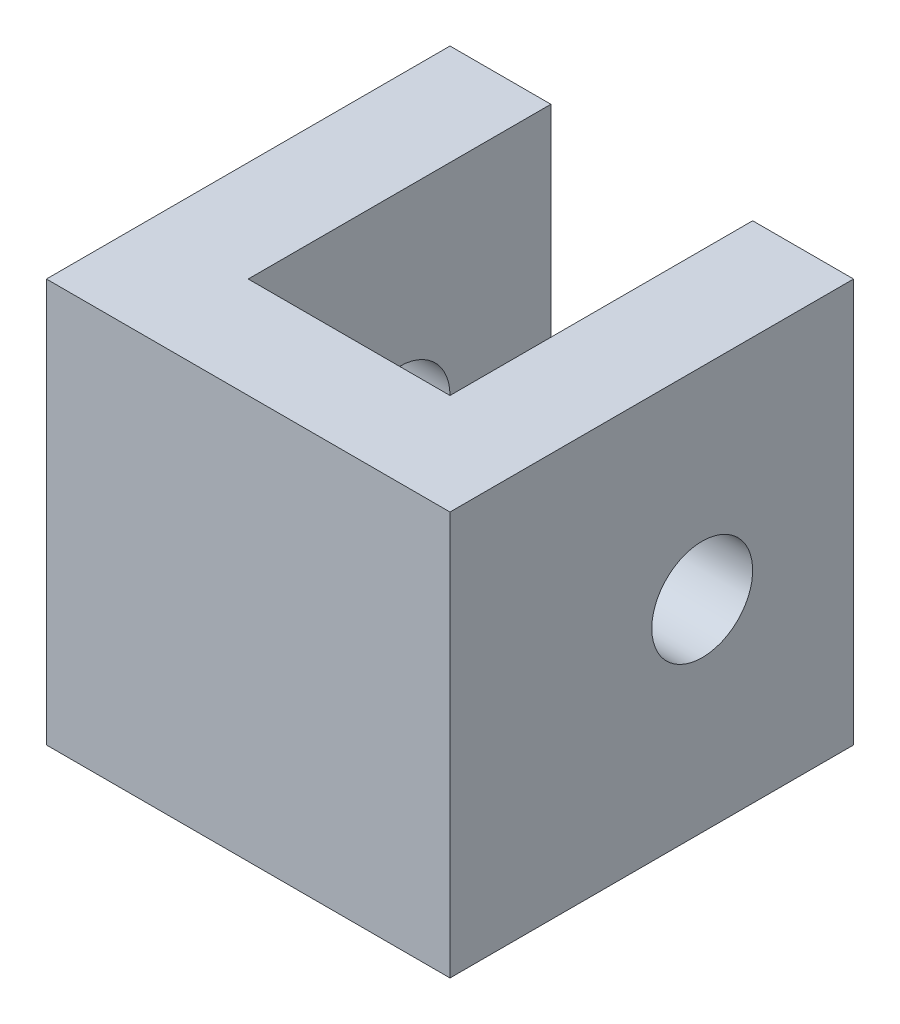
SolidWorks part; units mm, degrees
material "6061 Alloy"
ref_plane "Front Plane" through (0, 0, 0) normal (0, 0, 1) x (1, 0, 0)
ref_plane "Top Plane" through (0, 0, 0) normal (0, 1, 0) x (1, 0, 0)
ref_plane "Right Plane" through (0, 0, 0) normal (1, 0, 0) x (0, 0, -1)
sketch "Sketch1" plane through (0, 0, 0) normal (0, 1, 0) x (1, 0, 0)
  line L0 (-24.6455, -5.847) -> (0.7545, -5.847)
  line L1 (0.7545, -5.847) -> (0.7545, 19.553)
  line L2 (0.7545, 19.553) -> (-5.5955, 19.553)
  line L3 (-5.5955, 19.553) -> (-5.5955, 0.503)
  line L4 (-5.5955, 0.503) -> (-18.2955, 0.503)
  line L5 (-18.2955, 0.503) -> (-18.2955, 19.553)
  line L6 (-18.2955, 19.553) -> (-24.6455, 19.553)
  line L7 (-24.6455, 19.553) -> (-24.6455, -5.847)
  dimension "D1" = 6.35
  dimension "D2" = 12.7
  dimension "D3" = 19.05
  dimension "D4" = 6.35
extrude "Boss-Extrude1" add sketch "Sketch1" along normal blind 12.7 and the other way blind 12.7 contours L7 L0 L1 L2 L3 L4 L5 L6
sketch "Sketch3" plane through (-24.6455, 0, 0) normal (-1, 0, 0) x (0, 0, 1)
  line L1 (-10.028, -12.7) -> (-10.028, 0)
  line L2 (-19.553, -12.7) -> (5.847, -12.7) construction
  line L3 (-10.028, 0) -> (-10.028, 12.7)
  line L4 (-19.553, 12.7) -> (5.847, 12.7) construction
  line L6 (-19.553, -12.7) -> (-19.553, 12.7) construction
  circle A0 centre (-10.028, 0) radius 3.175
  dimension "D2" = 6.35
  dimension "D1" = 3.175
extrude "Cut-Extrude1" cut sketch "Sketch3" against normal through all contours L3 A0 L1 | L1 A0 L3 region at (-24.6455, 0, -11.3755) region at (-24.6455, 0, -8.6805)
sketch "Sketch4" plane through (0, 0, 5.847) normal (0, 0, 1) x (1, 0, 0)
  line L0 (-24.6455, -12.7) -> (0.7545, -12.7) construction
  line L1 (-24.6455, -12.7) -> (-24.6455, 12.7) construction
  circle A0 centre (-11.9455, 0) radius 6.35
  dimension "D1" = 12.7
  dimension "D2" = 12.7
  dimension "D3" = 12.7
